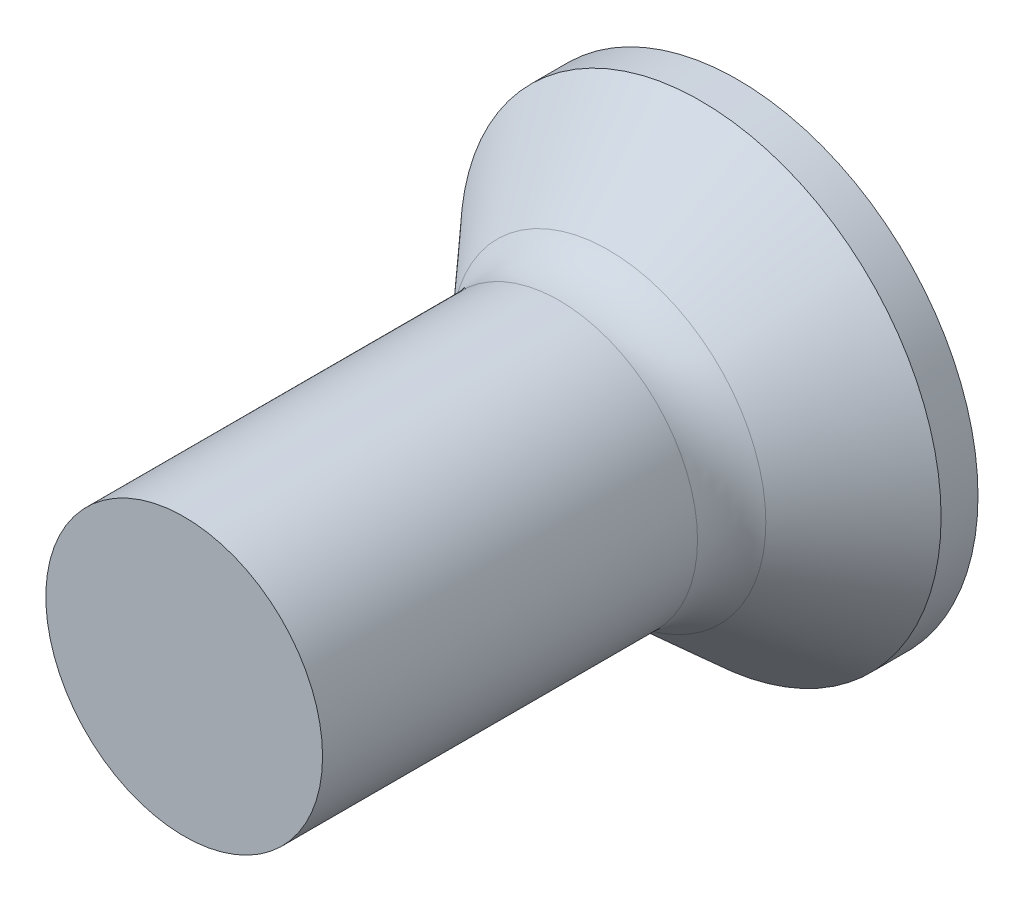
SolidWorks part; units mm, degrees
ref_plane "Спереди" through (0, 0, 0) normal (0, 0, 1) x (1, 0, 0)
ref_plane "Сверху" through (0, 0, 0) normal (0, 1, 0) x (1, 0, 0)
ref_plane "Справа" through (0, 0, 0) normal (1, 0, 0) x (0, 0, -1)
sketch "Эскиз1" plane through (0, 0, 0) normal (1, 0, 0) x (0, 0, -1)
  line L0 (-3, 0) -> (3, 0)
  line L1 (3, 0) -> (3, 2.6054)
  line L2 (3, 2.6054) -> (2.6, 2.6054)
  line L3 (2.6, 2.6054) -> (1.6, 1.7054)
  line L4 (1.0648, 1.5) -> (-3, 1.5)
  line L5 (-3, 1.5) -> (-3, 0)
  line L6 (3, 0) -> (3.2916, 0) construction
  arc A0 (1.0648, 1.5) -> (1.6, 1.7054) centre (1.0648, 2.3) ccw
  dimension "D3" = 0.8
  dimension "D1" = 3
  dimension "D2" = 6
  dimension "D4" = 0.9
  dimension "D5" = 0.4
  dimension "D6" = 1
revolve "Повернуть1" add sketch "Эскиз1" angle 360 about L6
sketch "Эскиз2" plane through (0, 0, 0) normal (1, 0, 0) x (0, 0, -1)
  line L0 (0, 0) -> (3, 0) construction
  line L1 (3, 0) -> (3, 1.4972)
  line L2 (3, 1.4972) -> (1, 0.5)
  line L3 (1, 0.5) -> (1, 0)
  line L4 (1, 0) -> (3, 0)
  line L5 (3, -2.6054) -> (3, 2.6054) construction
  dimension "D1" = 0.5
  dimension "D2" = 26.5
  dimension "D3" = 2
extrude "Вырез-Вытянуть1" cut sketch "Эскиз2" against normal blind 0.35 and the other way blind 0.35
pattern_circular "Круговой массив1" count 4 over 360 about axis through (0, 0, -3) along (0, 0, 1) of "Вырез-Вытянуть1"
sketch "Эскиз3" plane through (0, 0, 0) normal (1, 0, 0) x (0, 0, -1)
  line L0 (0, 0) -> (3.5491, 0) construction
  line L1 (0.8, 0) -> (0.9787, 0.55)
  line L2 (0.9787, 0.55) -> (3, 0.55)
  line L3 (3, 0.55) -> (3, 0)
  line L4 (3, 0) -> (0.8, 0)
  line L5 (3, -2.6054) -> (3, 2.6054) construction
  dimension "D1" = 72
  dimension "D2" = 2.2
  dimension "D3" = 1.1
revolve "Вырез-Повернуть1" cut sketch "Эскиз3" angle 360 about L0
